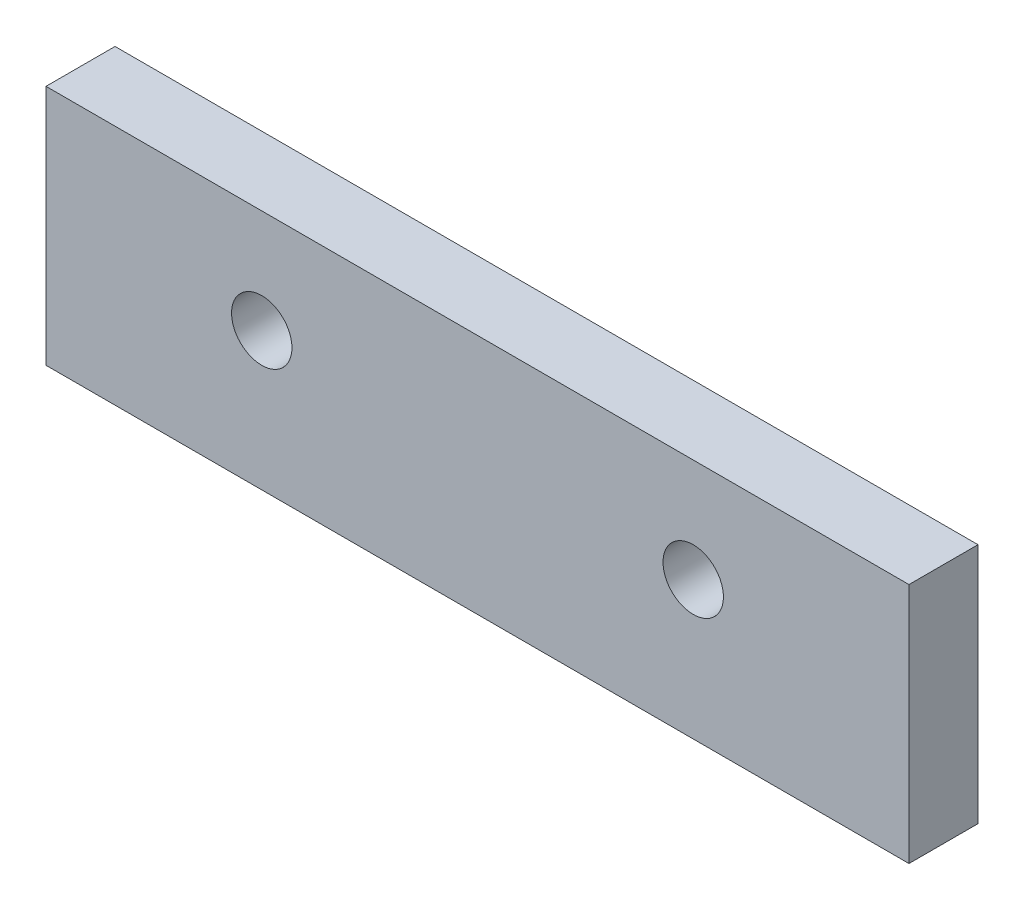
SolidWorks part; units mm, degrees
ref_plane "Front Plane" through (0, 0, 0) normal (0, 0, 1) x (1, 0, 0)
ref_plane "Top Plane" through (0, 0, 0) normal (0, 1, 0) x (1, 0, 0)
ref_plane "Right Plane" through (0, 0, 0) normal (1, 0, 0) x (0, 0, -1)
sketch "Sketch1" plane through (0, 0, 0) normal (0, 0, 1) x (1, 0, 0)
  line L1 (0, 0) -> (50, 0)
  line L2 (0, 0) -> (0, 14)
  line L3 (0, 14) -> (50, 14)
  line L4 (50, 0) -> (50, 14)
  circle A0 centre (12.5, 8) radius 1.75
  circle A1 centre (37.5, 8) radius 1.75
  dimension "D3" = 3.5
  dimension "D1" = 14
  dimension "D2" = 50
  dimension "D4" = 12.5
  dimension "D5" = 25
  dimension "D6" = 12.5
  dimension "D7" = 6
extrude "Boss-Extrude1" add sketch "Sketch1" along normal blind 4
equation "\"LinearRailHoleDistance\"= 25mm'Spec"
equation "\"D5@Sketch1\"=\"LinearRailHoleDistance\""
equation "\"D2@Sketch1\"=\"LinearRailHoleDistance\" * 2"
equation "\"D4@Sketch1\"=\"LinearRailHoleDistance\"/2"
equation "\"LinearRailHoleDiameter\"= 3.5mm'Spec"
equation "\"D3@Sketch1\"=\"LinearRailHoleDiameter\""
equation "\"LinearRailHeight\"= 8mm'Spec"
equation "\"LinearRailWidth\"= 12mm'Spec"
equation "\"D1@Sketch1\"=\"LinearRailWidth\"+2mm"
equation "\"D1@Boss-Extrude1\"=\"LinearRailHeight\"/2"
equation "\"D7@Sketch1\"=\"LinearRailWidth\"/2"
